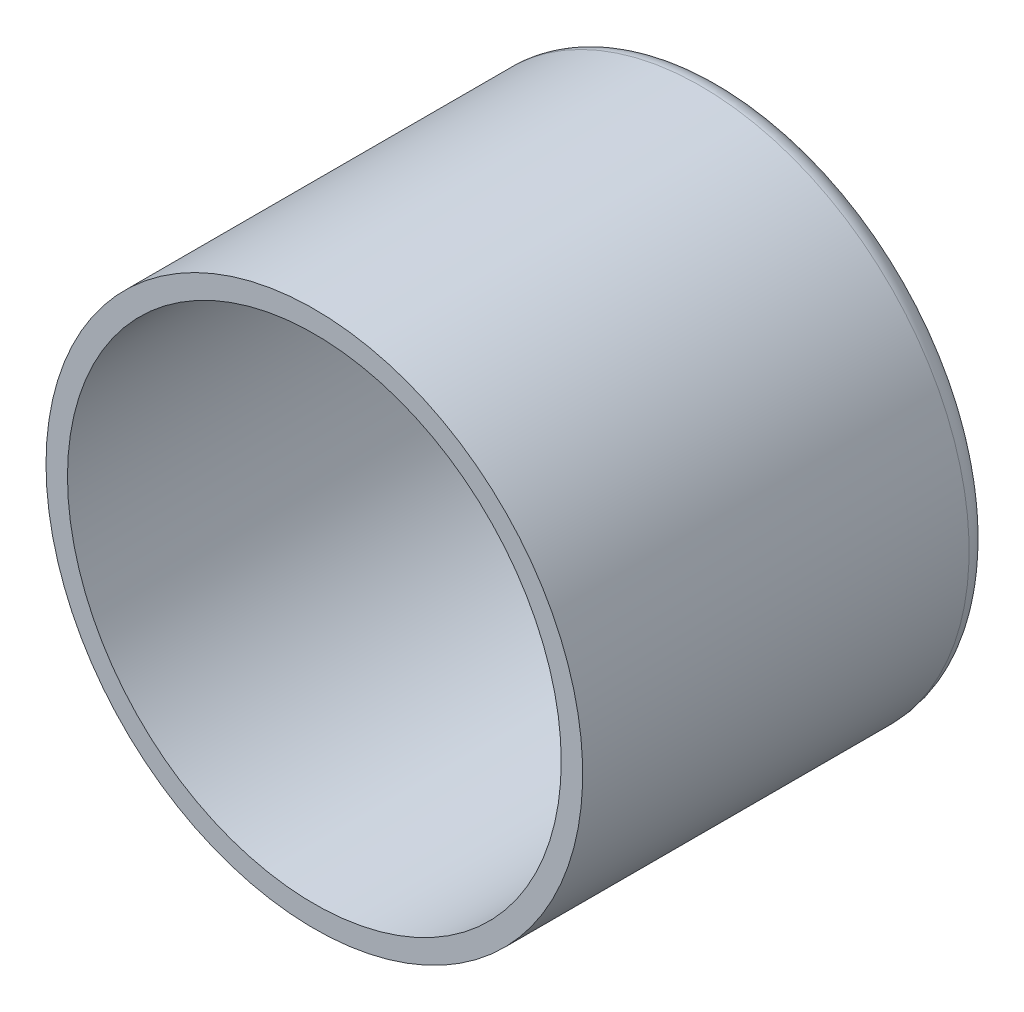
SolidWorks part; units mm, degrees
ref_plane "前视基准面" through (0, 0, 0) normal (0, 0, 1) x (1, 0, 0)
ref_plane "上视基准面" through (0, 0, 0) normal (0, 1, 0) x (1, 0, 0)
ref_plane "右视基准面" through (0, 0, 0) normal (1, 0, 0) x (0, 0, -1)
sketch "草图1" plane through (0, 0, 0) normal (0, 0, 1) x (1, 0, 0)
  circle A0 centre (0, 0) radius 23
  circle A1 centre (0, 0) radius 25
extrude "凸台-拉伸1" add sketch "草图1" along normal blind 40
sketch "草图2" plane through (0, 0, 0) normal (0, 0, -1) x (-1, 0, 0)
  circle A0 centre (0, 0) radius 25
extrude "凸台-拉伸2" add sketch "草图2" along normal blind 2
sketch "草图3" plane through (0, 0, -2) normal (0, 0, -1) x (-1, 0, 0)
  circle A0 centre (0, 0) radius 16.5
extrude "切除-拉伸1" cut sketch "草图3" against normal blind 2
fillet "圆角1" radius 2 1 edges at (-25, 0, -2)
fillet "圆角2" radius 2 1 edges at (23, 0, 0)
fillet "圆角3" radius 2 1 edges at (-16.5, 0, -2)
sketch "草图4" plane through (0, 0, 40) normal (0, 0, 1) x (1, 0, 0)
  line L1 (30.786, 37.1072) -> (-30.9227, 37.1072)
  line L2 (30.786, 37.1072) -> (30.786, -44.556)
  line L3 (30.786, -44.556) -> (-30.9227, -44.556)
  line L4 (-30.9227, 37.1072) -> (-30.9227, -44.556)
extrude "切除-拉伸2" cut sketch "草图4" against normal blind 4
